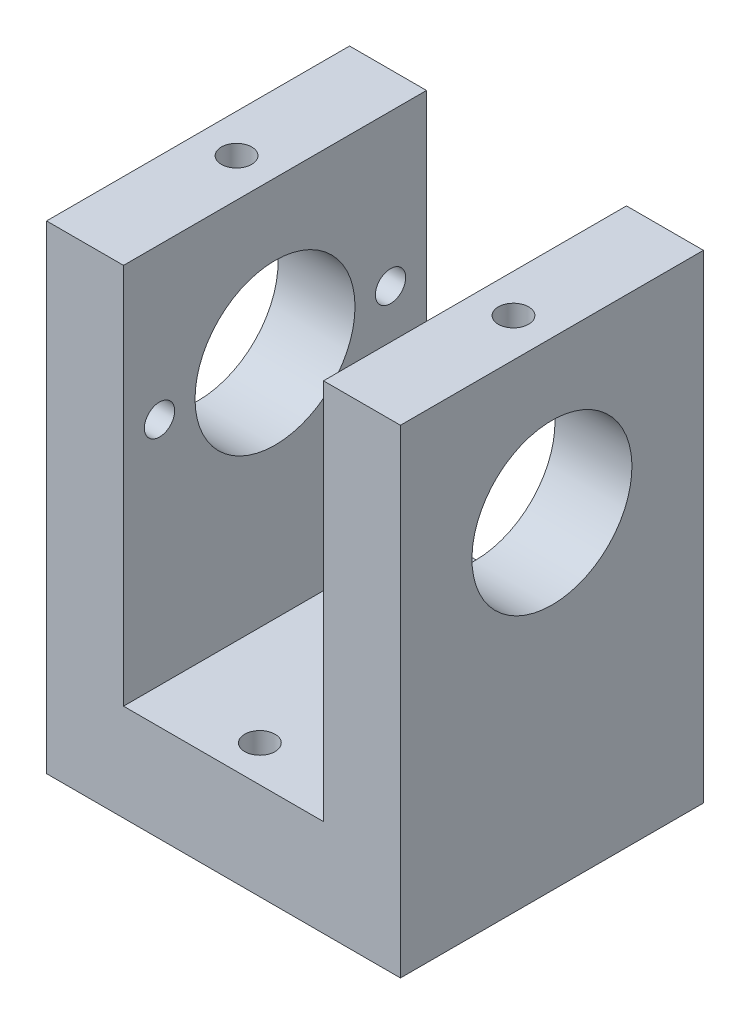
SolidWorks part; units mm, degrees
material "6061 Alloy"
ref_plane "Front Plane" through (0, 0, 0) normal (0, 0, 1) x (1, 0, 0)
ref_plane "Top Plane" through (0, 0, 0) normal (0, 1, 0) x (1, 0, 0)
ref_plane "Right Plane" through (0, 0, 0) normal (1, 0, 0) x (0, 0, -1)
sketch "Sketch1" plane through (0, 0, 0) normal (0, 0, 1) x (1, 0, 0)
  line L0 (-14.6, 12.5) -> (-14.6, -27)
  line L1 (-14.6, -27) -> (14.6, -27)
  line L2 (14.6, -27) -> (14.6, 12.5)
  line L3 (-8.25, 12.5) -> (-8.25, -19)
  line L4 (-8.25, -19) -> (8.25, -19)
  line L5 (8.25, -19) -> (8.25, 12.5)
  line L6 (-14.6, 12.5) -> (-8.25, 12.5)
  line L7 (8.25, 12.5) -> (14.6, 12.5)
  line L8 (0, -19) -> (0, -27) construction
  line L9 (14.6, -27) -> (14.6, 28.7745) construction
  dimension "D1" = 8
  dimension "D2" = 0
  dimension "D3" = 29.2
  dimension "D4" = 39.5
  dimension "D5" = 39.5
  dimension "D6" = 27
  dimension "D7" = 6.35
extrude "Boss-Extrude1" add sketch "Sketch1" along normal blind 12.5 and the other way blind 12.5
sketch "Sketch3" plane through (-14.6, 0, 0) normal (-1, 0, 0) x (0, 0, 1)
  circle A0 centre (0, 0) radius 6.6
  dimension "D3" = 13.2
extrude "Cut-Extrude1" cut sketch "Sketch3" against normal through all
hole_wizard "Tap Drill for M3x0.5 Tap3" positions "Sketch12" profile "Sketch13" hole size "M3x0.5" standard "ANSI Metric"
sketch "Sketch12" plane through (0, 12.5, 0) normal (0, 1, 0) x (1, 0, 0)
  line L0 (-14.6, 12.5) -> (-14.6, -12.5) construction
  line L1 (-8.25, 12.5) -> (-14.6, 12.5) construction
  line L2 (14.6, 12.5) -> (8.25, 12.5) construction
  line L3 (14.6, 12.5) -> (14.6, -12.5) construction
  point P0 (-11.425, 0)
  point P2 (11.425, 0)
  dimension "D1" = 3.175
  dimension "D2" = 12.5
  dimension "D3" = 12.5
  dimension "D4" = 3.175
sketch "Sketch13" plane through (-11.425, 12.5, 0) normal (1, 0, 0) x (0, 0, 1)
  line L0 (0, 0) -> (0, 7.7511)
  line L1 (0, 7.7511) -> (1.25, 7)
  line L2 (1.25, 7) -> (1.25, 0)
  line L5 (1.25, 0) -> (0, 0)
  line L10 (0, 7.7511) -> (-1.25, 7) construction
  line L11 (0, -6.35) -> (0, 107.95) construction
  dimension "Hole Dia." = 2.5
  dimension "Hole Depth" = 7
  dimension "Drill Angle" = 118
hole_wizard "Tap Drill for M4x0.7 Tap1" positions "Sketch15" profile "Sketch16" hole size "M4x0.7" standard "ANSI Metric"
sketch "Sketch15" plane through (0, -27, 0) normal (0, -1, 0) x (-1, 0, 0)
  line L0 (-14.6, 12.5) -> (-14.6, -12.5) construction
  line L1 (14.6, 12.5) -> (14.6, -12.5) construction
  point P0 (-10.1, 0)
  point P2 (10.1, 0)
  point P19 (0, 0)
  point P20 (0, 0)
  dimension "D1" = 4.5
  dimension "D2" = 4.5
sketch "Sketch16" plane through (10.1, -27, 0) normal (1, 0, 0) x (0, 0, -1)
  line L0 (0, 0) -> (0, 8.9914)
  line L1 (0, 8.9914) -> (1.65, 8)
  line L2 (1.65, 8) -> (1.65, 0)
  line L5 (1.65, 0) -> (0, 0)
  line L10 (0, 8.9914) -> (-1.65, 8) construction
  line L11 (0, -6.35) -> (0, 107.95) construction
  dimension "Hole Dia." = 3.3
  dimension "Hole Depth" = 8
  dimension "Drill Angle" = 118
hole_wizard "Tap Drill for M3x0.5 Tap4" positions "Sketch17" profile "Sketch19" hole size "M3x0.5" standard "ANSI Metric" end condition up to next
sketch "Sketch17" plane through (-14.6, 0, 0) normal (-1, 0, 0) x (0, 0, 1)
  line L0 (-12.5, 12.5) -> (-12.5, -27) construction
  line L1 (12.5, 12.5) -> (12.5, -27) construction
  point P0 (-9.53, 0)
  point P2 (9.53, 0)
  dimension "D1" = 2.97
  dimension "D2" = 2.97
sketch "Sketch19" plane through (-14.6, 0, -9.53) normal (0, 1, 0) x (0, 0, 1)
  line L0 (0, 0) -> (0, 6.35)
  line L1 (0, 6.35) -> (1.25, 6.35)
  line L2 (1.25, 6.35) -> (1.25, 0)
  line L5 (1.25, 0) -> (0, 0)
  line L11 (0, -6.35) -> (0, 107.95) construction
  dimension "Thru Hole Dia." = 2.5
  dimension "Thru Hole Depth" = 6.35
hole_wizard "Tap Drill for M3x0.5 Tap5" positions "Sketch21" profile "Sketch22" hole size "M3x0.5" standard "ANSI Metric" end condition up to next
sketch "Sketch21" plane through (0, -27, 0) normal (0, -1, 0) x (-1, 0, 0)
  line L0 (14.6, -12.5) -> (-14.6, -12.5) construction
  point P0 (0, -9.5)
  point P2 (0, 9.5)
  dimension "D1" = 19
  dimension "D2" = 3
sketch "Sketch22" plane through (0, -27, 9.5) normal (1, 0, 0) x (0, 0, -1)
  line L0 (0, 0) -> (0, 8)
  line L1 (0, 8) -> (1.25, 8)
  line L2 (1.25, 8) -> (1.25, 0)
  line L5 (1.25, 0) -> (0, 0)
  line L11 (0, -6.35) -> (0, 107.95) construction
  dimension "Thru Hole Dia." = 2.5
  dimension "Thru Hole Depth" = 8
